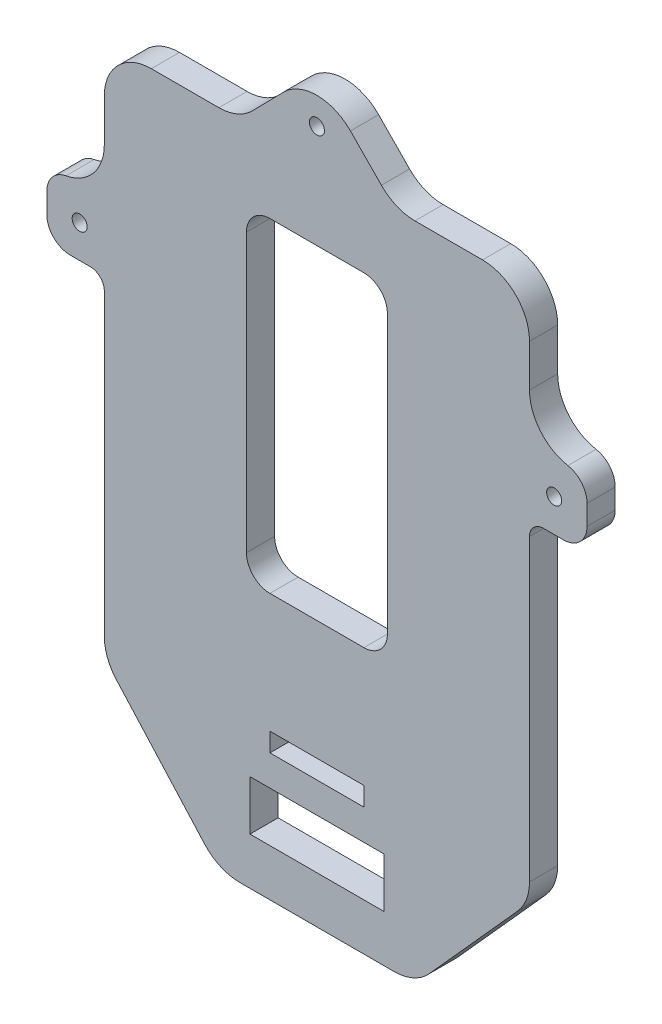
SolidWorks part; units mm, degrees
material "MDF"
ref_plane "Plano frontal" through (0, 0, 0) normal (0, 0, 1) x (1, 0, 0)
ref_plane "Plano superior" through (0, 0, 0) normal (0, 1, 0) x (1, 0, 0)
ref_plane "Plano direito" through (0, 0, 0) normal (1, 0, 0) x (0, 0, -1)
sketch "Esboço1" plane through (0, 0, 0) normal (0, 0, 1) x (1, 0, 0)
  line L1 (-45.25, -56.75) -> (45.25, -56.75) construction
  line L2 (-45.25, -56.75) -> (-45.25, 56.75) construction
  line L3 (-45.25, 56.75) -> (45.25, 56.75) construction
  line L4 (45.25, -56.75) -> (45.25, 13.75) construction
  line L5 (-45.25, -56.75) -> (45.25, 56.75) construction
  line L6 (-45.25, 56.75) -> (45.25, -56.75) construction
  line L18 (-45.25, -56.75) -> (21.552, -56.75) construction
  line L20 (-45.25, -56.75) -> (-20.9068, -83.85)
  line L21 (-20.9068, -83.85) -> (20.9068, -83.85)
  line L23 (14.25, -63.25) -> (-14.25, -63.25)
  line L24 (14.25, -63.25) -> (14.25, -73.85)
  line L25 (14.25, -73.85) -> (-14.25, -73.85)
  line L26 (-14.25, -63.25) -> (-14.25, -73.85)
  line L27 (14.25, -63.25) -> (-14.25, -73.85) construction
  line L28 (14.25, -73.85) -> (-14.25, -63.25) construction
  line L29 (-15.1, -75.35) -> (15.1, -75.35) construction
  line L30 (-15.1, -75.35) -> (-15.1, -61.75) construction
  line L31 (-15.1, -61.75) -> (15.1, -61.75) construction
  line L32 (15.1, -75.35) -> (15.1, -61.75) construction
  line L33 (-15.1, -75.35) -> (15.1, -61.75) construction
  line L34 (-15.1, -61.75) -> (15.1, -75.35) construction
  line L39 (-45.25, 27.75) -> (-45.25, 56.75)
  line L48 (15, -27.35) -> (-15, -27.35)
  line L50 (-45.25, 27.75) -> (-57.5, 27.75)
  line L52 (0, 0) -> (0, 36.35) construction
  line L54 (45.25, 27.75) -> (57.5, 27.75)
  line L55 (45.25, 27.75) -> (45.25, 56.75)
  line L56 (45.25, 27.75) -> (45.25, 56.75) construction
  line L57 (-45.25, 56.75) -> (-16.6633, 56.75)
  line L58 (-16.6633, 56.75) -> (0, 73.75)
  line L59 (0, 73.75) -> (16.6633, 56.75)
  line L60 (16.6633, 56.75) -> (45.25, 56.75)
  line L61 (-57.5, 27.75) -> (-57.5, 13.75)
  line L62 (-57.5, 13.75) -> (-45.25, 13.75)
  line L63 (57.5, 13.75) -> (45.25, 13.75)
  line L64 (57.5, 27.75) -> (57.5, 13.75)
  line L65 (20.9068, -83.85) -> (45.25, -56.75)
  line L66 (45.25, 13.75) -> (45.25, -56.75)
  line L67 (-45.25, -56.75) -> (-45.25, 13.75)
  line L68 (15, -27.35) -> (15, 41.75)
  line L69 (10, -52.75) -> (-10, -52.75)
  line L70 (10, -52.75) -> (10, -56.75)
  line L71 (10, -56.75) -> (-10, -56.75)
  line L72 (-10, -52.75) -> (-10, -56.75)
  line L73 (10, -52.75) -> (-10, -56.75) construction
  line L74 (10, -56.75) -> (-10, -52.75) construction
  line L75 (15, 41.75) -> (-15, 41.75)
  line L76 (-15, -27.35) -> (-15, 41.75)
  line L77 (15, -27.35) -> (-15, 41.75) construction
  line L78 (15, 41.75) -> (-15, -27.35) construction
  circle A0 centre (0, 63.75) radius 1.6
  circle A1 centre (-50.5, -80.53) radius 1.6
  circle A2 centre (-50.5, 20.75) radius 1.6
  circle A3 centre (50.5, 20.75) radius 1.6
  point P0 (0, 0)
  point P6 (0, -54.75)
  point P16 (0, -83.85)
  point P27 (0, -68.55)
  point P32 (0, -68.55)
  point P39 (0, 0)
  point P42 (0, 7.2)
  dimension "D3" = 3.2
  dimension "D10" = 10
  dimension "D4" = 7
  dimension "D5" = 10
  dimension "D9" = 43
  dimension "D19" = 101
  dimension "D1" = 90.5
  dimension "D2" = 113.5
  dimension "D6" = 7
  dimension "D7" = 5
  dimension "D8" = 10
  dimension "D11" = 28.5
  dimension "D12" = 10.6
  dimension "D13" = 13.6
  dimension "D14" = 30.2
  dimension "D15" = 7
  dimension "D16" = 144.28
  dimension "D17" = 25.4
  dimension "D18" = 7
  dimension "D20" = 15
  dimension "D21" = 20
  dimension "D22" = 7
  dimension "D23" = 4
  dimension "D24" = 30
extrude "Ressalto-extrusão1" add sketch "Esboço1" along normal blind 6 contours L23 L24 L25 | L26 L23 L25 A2 A1 A0 region at (-43.299, -21.5, 0)
fillet "Filete3" radius 3 2 edges at (45.25, 13.75, 3) (-45.25, 13.75, 3)
fillet "Filete4" radius 10 11 edges at (-16.6633, 56.75, 3) (16.6633, 56.75, 3) (-45.25, 27.75, 3) (45.25, 27.75, 3) (0, 73.75, 3) (45.25, 56.75, 3) (-45.25, 56.75, 3) (-45.25, -56.75, 3) (45.25, -56.75, 3) (20.9068, -83.85, 3) (-20.9068, -83.85, 3)
fillet "Filete5" radius 5 8 edges at (57.5, 13.75, 3) (57.5, 27.75, 3) (-57.5, 13.75, 3) (-57.5, 27.75, 3) (-15, -27.35, 3) (15, -27.35, 3) (15, 41.75, 3) (-15, 41.75, 3)
equation "\"mm\"=5"
